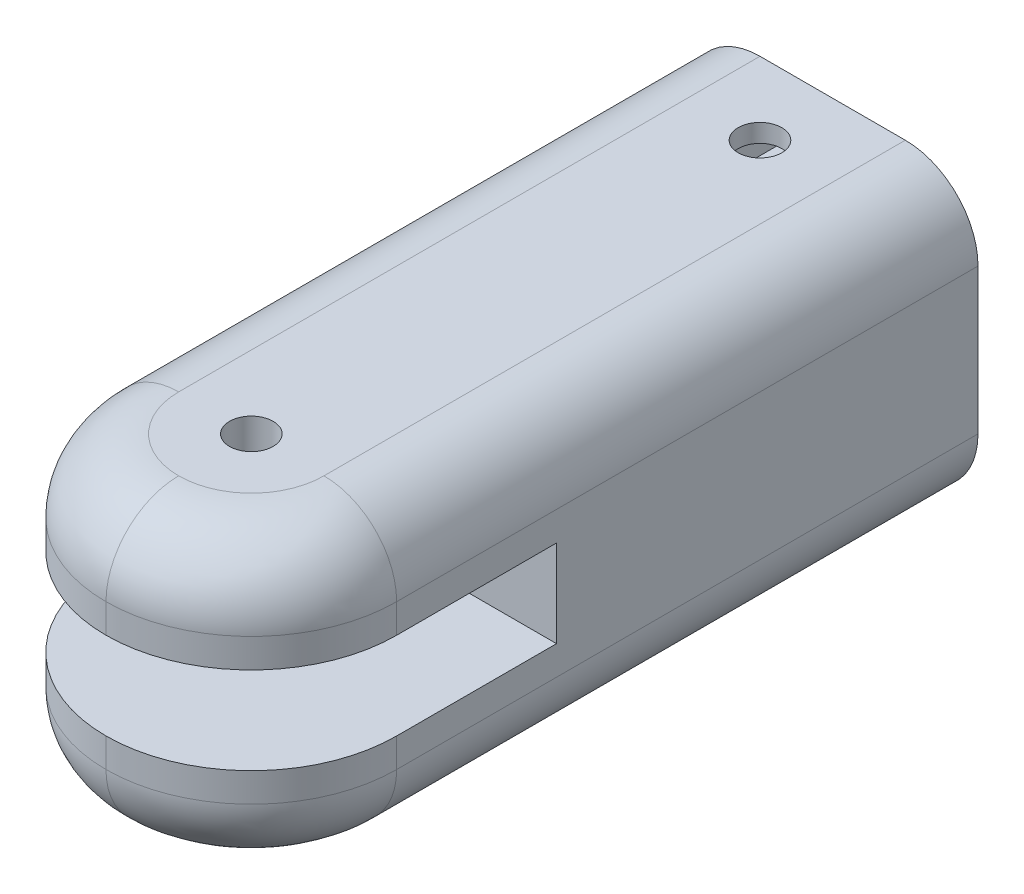
SolidWorks part; units mm, degrees
material "ABS"
ref_plane "Front Plane" through (0, 0, 0) normal (0, 0, 1) x (1, 0, 0)
ref_plane "Top Plane" through (0, 0, 0) normal (0, 1, 0) x (1, 0, 0)
ref_plane "Right Plane" through (0, 0, 0) normal (1, 0, 0) x (0, 0, -1)
sketch "Sketch1" plane through (0, 0, 0) normal (0, 0, 1) x (1, 0, 0)
  line L0 (10, 20) -> (10, 0) construction
  line L1 (0, 0) -> (20, 0)
  line L2 (0, 0) -> (0, 20)
  line L3 (0, 20) -> (20, 20)
  line L4 (20, 0) -> (20, 20)
  line L5 (0, 10) -> (20, 10) construction
  circle A0 centre (10, 10) radius 5.3
  dimension "D2" = 10.6
  dimension "D1" = 20
extrude "Boss-Extrude1" add sketch "Sketch1" along normal blind 25
sketch "Sketch2" plane through (0, 0, 25) normal (0, 0, 1) x (1, 0, 0)
  line L4 (0, 20) -> (0, 0)
  line L5 (0, 0) -> (20, 0)
  line L6 (20, 0) -> (20, 20)
  line L7 (20, 20) -> (0, 20)
  line L8 (0, 20) -> (0, 0)
  line L9 (0, 0) -> (20, 0)
  line L10 (20, 0) -> (20, 20)
  line L11 (20, 20) -> (0, 20)
  dimension "D1" = 0
extrude "Boss-Extrude2" add sketch "Sketch2" along normal blind 25
sketch "Sketch4" plane through (0, 0, 50) normal (0, 0, 1) x (1, 0, 0)
  line L0 (10, 20) -> (10, 0) construction
  line L1 (20, 20) -> (0, 20) construction
  line L2 (0, 0) -> (20, 0) construction
  line L3 (0, 10) -> (20, 10) construction
  line L4 (0, 20) -> (0, 0) construction
  line L5 (20, 0) -> (20, 20) construction
  line L6 (0, 7) -> (0, 13)
  line L7 (0, 13) -> (20, 13)
  line L8 (20, 13) -> (20, 7)
  line L9 (0, 7) -> (20, 7)
  dimension "D1" = 3
extrude "Cut-Extrude1" cut sketch "Sketch4" against normal blind 21
sketch "Sketch5" plane through (0, 20, 0) normal (0, 1, 0) x (1, 0, 0)
  line L0 (10, 0) -> (10, -50) construction
  line L1 (20, 0) -> (0, 0) construction
  line L2 (20, -50) -> (0, -50) construction
  circle A0 centre (10, -5) radius 1.5
  circle A1 centre (10, -40) radius 1.5
  dimension "D1" = 3
  dimension "D2" = 35
  dimension "D3" = 10
extrude "Cut-Extrude2" cut sketch "Sketch5" against normal up to surface (20 mm away) up to face at (10, 0, 25)
fillet "Fillet2" radius 10 4 edges at (0, 16.5, 50) (0, 3.5, 50) (20, 3.5, 50) (20, 16.5, 50)
fillet "Fillet3" radius 5 8 edges at (0, 20, 20) (2.9289, 20, 47.0711) (17.0711, 20, 47.0711) (0, 0, 20) (2.9289, 0, 47.0711) (17.0711, 0, 47.0711) (20, 20, 20) (20, 0, 20)
sketch "Sketch6" plane through (0, 0, 0) normal (0, 0, -1) x (-1, 0, 0)
  line L0 (-10, 20) -> (-10, 0) construction
  line L1 (-12.825, 18.75) -> (-7.175, 18.75)
  line L2 (-12.825, 18.75) -> (-12.825, 16.25)
  line L3 (-12.825, 16.25) -> (-7.175, 16.25)
  line L4 (-7.175, 18.75) -> (-7.175, 16.25)
  line L5 (-5, 0) -> (-15, 0) construction
  line L6 (-20, 10) -> (0, 10) construction
  line L7 (-20, 5) -> (-20, 15) construction
  line L8 (0, 15) -> (0, 5) construction
  line L9 (-10, 18.75) -> (-10, 16.25) construction
  line L10 (-12.825, 17.5) -> (-7.175, 17.5) construction
  line L11 (-12.825, 2.5) -> (-7.175, 2.5) construction
  line L12 (-12.825, 3.75) -> (-7.175, 3.75)
  line L13 (-7.175, 1.25) -> (-7.175, 3.75)
  line L14 (-12.825, 1.25) -> (-7.175, 1.25)
  line L15 (-12.825, 1.25) -> (-12.825, 3.75)
  line L16 (-10, 1.25) -> (-10, 3.75) construction
  dimension "D1" = 5.65
  dimension "D2" = 2.5
  dimension "D3" = 7.5
extrude "Cut-Extrude3" cut sketch "Sketch6" against normal blind 8
chamfer "Chamfer1" distance 1 angle 45 4 edges at (12.825, 2.5, 8) (7.175, 2.5, 8) (7.175, 17.5, 8) (12.825, 17.5, 8)
